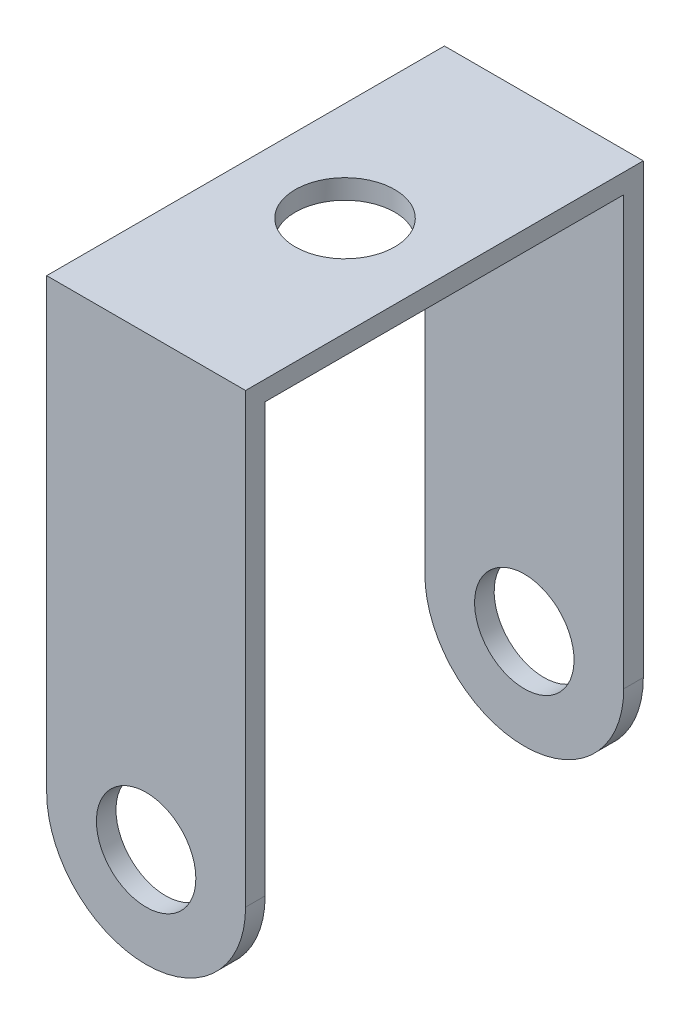
SolidWorks part; units mm, degrees
ref_plane "Front Plane" through (0, 0, 0) normal (0, 0, 1) x (1, 0, 0)
ref_plane "Top Plane" through (0, 0, 0) normal (0, 1, 0) x (1, 0, 0)
ref_plane "Right Plane" through (0, 0, 0) normal (1, 0, 0) x (0, 0, -1)
sketch "Sketch1" plane through (0, 0, 0) normal (0, 0, 1) x (1, 0, 0)
  line L2 (-25.4, 0) -> (-25.4, 114.3)
  line L3 (-25.4, 114.3) -> (25.4, 114.3)
  line L4 (25.4, 0) -> (25.4, 114.3)
  arc A0 (-25.4, 0) -> (25.4, 0) centre (0, 0) ccw
  circle A1 centre (0, 0) radius 12.7
  dimension "D2" = 50.8
  dimension "D4" = 25.4
  dimension "D3" = 25.4
  dimension "D5" = 114.3
extrude "Boss-Extrude1" add sketch "Sketch1" along normal mid plane 101.6
sketch "Sketch2" plane through (25.4, 0, 0) normal (1, 0, 0) x (0, 0, -1)
  line L0 (-50.8, 0) -> (-50.8, 114.3) construction
  line L1 (-45.8, 109.3) -> (45.8, 109.3)
  line L2 (-45.8, 109.3) -> (-45.8, -25.4)
  line L3 (-45.8, -25.4) -> (45.8, -25.4)
  line L4 (45.8, 109.3) -> (45.8, -25.4)
  line L5 (-50.8, 114.3) -> (50.8, 114.3) construction
  line L6 (50.8, 0) -> (50.8, 114.3) construction
  line L7 (-50.8, 0) -> (50.8, 0) construction
  point P12 (0, 0)
  dimension "D1" = 5
  dimension "D2" = 5
  dimension "D3" = 5
  dimension "D4" = 25.4
extrude "Cut-Extrude1" cut sketch "Sketch2" against normal blind 101.6
sketch "Sketch3" plane through (0, 114.3, 0) normal (0, 1, 0) x (1, 0, 0)
  circle A0 centre (0, 0) radius 12.7
  dimension "D1" = 25.4
extrude "Cut-Extrude2" cut sketch "Sketch3" against normal blind 101.6 contours A0
ref_axis "Axis2" through (0, -57.483, 0) along (0, 1, 0)
ref_axis "Axis3" through (0, 0, 112.553) along (0, 0, -1)
